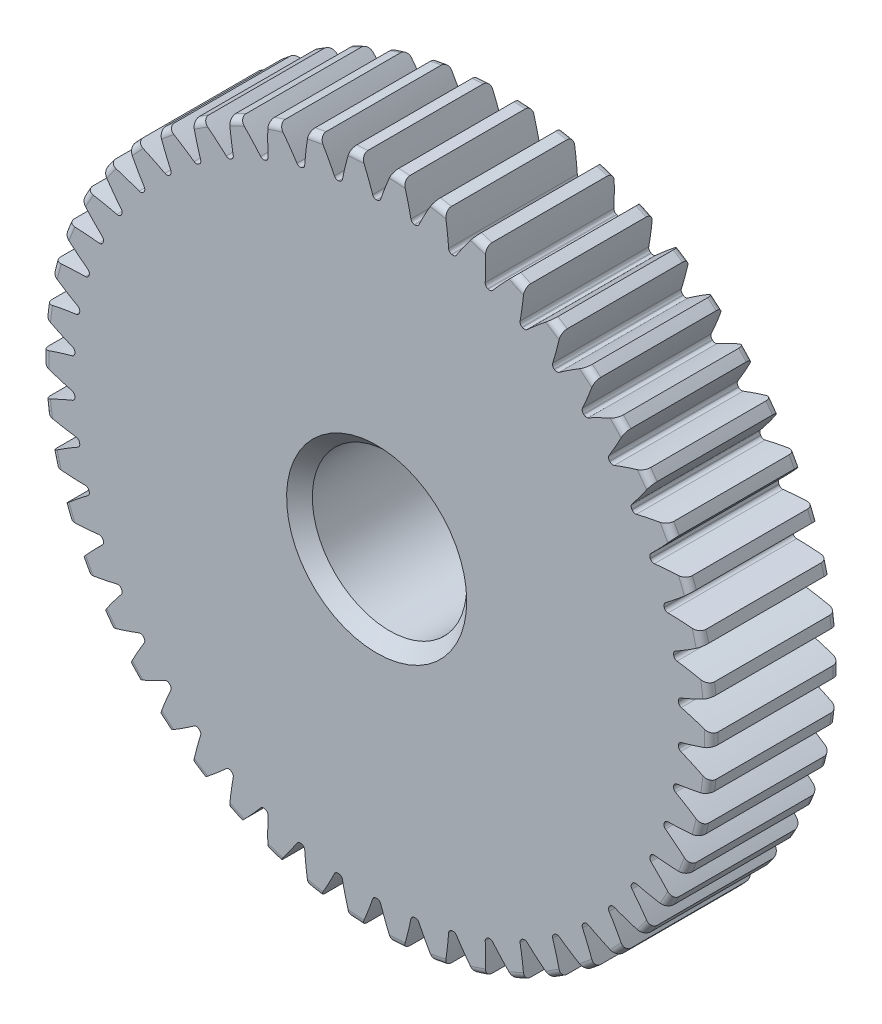
SolidWorks part; units mm, degrees
ref_plane "Front Plane" through (0, 0, 0) normal (0, 0, 1) x (1, 0, 0)
ref_plane "Top Plane" through (0, 0, 0) normal (0, 1, 0) x (1, 0, 0)
ref_plane "Right Plane" through (0, 0, 0) normal (1, 0, 0) x (0, 0, -1)
sketch "Sketch1" plane through (0, 0, 0) normal (0, 0, 1) x (1, 0, 0)
  line L0 (-635, 0) -> (635, 0) construction
  circle A0 centre (0, 0) radius 33.02 construction
  circle A1 centre (0, 0) radius 31.75 construction
  circle A2 centre (0, 0) radius 29.845 construction
  circle A3 centre (0, 0) radius 20.574 construction
  circle A4 centre (0, 0) radius 6.35 construction
  dimension "D2" = 1.27
  dimension "D3" = 3.175
  dimension "D1" = 3.175
sketch "Sketch2" plane through (0, 0, 0) normal (1, 0, 0) x (0, 0, -1)
  line L0 (0, 0) -> (-12.7, 0) construction
  line L1 (-12.7, 0) -> (-25.4, 0) construction
  dimension "Overall Width" = 25.4
  dimension "Face Width" = 12.7
sketch "Sketch4" plane through (0, 0, 0) normal (1, 0, 0) x (0, 0, -1)
  line L0 (-25.4, 6.35) -> (-25.4, 20.574)
  line L1 (-25.4, 20.574) -> (-12.7, 20.574)
  line L2 (-12.7, 20.574) -> (-12.7, 33.02)
  line L3 (-12.7, 33.02) -> (0, 33.02)
  line L4 (0, 33.02) -> (0, 6.35)
  line L5 (-12.7, 20.574) -> (-12.7, 0) construction
  line L6 (0, 33.02) -> (0, -33.02) construction
  line L7 (-12.7, 20.574) -> (0, 20.574) construction
  line L12 (-25.4, 6.35) -> (0, 6.35)
revolve "Revolve1" add sketch "Sketch4" angle 360 about L1
fillet "Fillet2" radius 0.6604 4 edges at (0, 20.574, 25.4) (0, 20.574, 12.7) (0, 33.02, 12.7) (0, 33.02, 0)
sketch "Sketch7" plane through (0, 0, 12.7) normal (0, 0, 1) x (1, 0, 0)
  line L0 (0, 0) -> (0, 33.02) construction
  line L1 (0.9973, 31.7343) -> (1.4979, 32.986) construction
  line L3 (2.0733, 32.9548) -> (1.9936, 31.6873) construction
  line L4 (1.9936, 31.6873) -> (1.874, 29.7861) construction
  line L5 (0, 0) -> (1.874, 29.7861) construction
  line L6 (0.9973, 31.7343) -> (0, 0) construction
  line L7 (0.9973, 31.7343) -> (1.0372, 33.0037) construction
  line L8 (0.9973, 31.7343) -> (0, 0) construction
  circle A0 centre (0, 0) radius 33.02 construction
  arc A1 (-0.035, 29.845) -> (0.035, 29.845) centre (0, 0) cw
  circle A2 centre (0, 0) radius 29.845 construction
  arc A3 (-0.9973, 31.7343) -> (0.9973, 31.7343) centre (0, 0) cw construction
  circle A4 centre (0, 0) radius 31.75 construction
  arc A5 (2.6175, 32.9161) -> (1.5287, 32.9846) centre (0, 0) ccw construction
  arc A6 (0.9973, 31.7343) -> (2.9879, 31.6091) centre (0, 0) cw construction
  arc A7 (-1.5287, 32.9846) -> (1.5287, 32.9846) centre (0, 0) cw
  arc A8 (0.3964, 30.1041) -> (1.5287, 32.9846) centre (30.4767, 19.9434) cw
  arc A9 (-0.3964, 30.1041) -> (-1.5287, 32.9846) centre (-30.4767, 19.9434) ccw
  arc A10 (-0.035, 29.845) -> (-0.3964, 30.1041) centre (-0.0354, 30.226) cw
  arc A11 (0.035, 29.845) -> (0.3964, 30.1041) centre (0.0354, 30.226) ccw
  point P26 (-0.3096, 29.8434)
  point P29 (0.3096, 29.8434)
  dimension "D4" = 0.381
  dimension "D5" = 31.75
  dimension "D3" = 20
  dimension "D1" = 3.9898
  dimension "D2" = 1.9949
extrude "Cut-Extrude2" cut sketch "Sketch7" against normal through all
pattern_circular "CirPattern1" count 50 over 360 about axis through (0, 0, 25.4) along (0, 0, -1) of "Cut-Extrude2"
sketch "Sketch8" plane through (0, 0, 25.4) normal (0, 0, 1) x (1, 0, 0)
  circle A0 centre (0, 0) radius 22.86
  dimension "D1" = 45.72
extrude "Cut-Extrude3" cut sketch "Sketch8" against normal up to surface (12.7 mm away) up to face at (0, 0, 12.7)
sketch "Sketch9" plane through (0, 0, 12.7) normal (0, 0, 1) x (1, 0, 0)
  circle A0 centre (0, 0) radius 7.62
  dimension "D1" = 15.24
extrude "Cut-Extrude4" cut sketch "Sketch9" against normal up to next
chamfer "Chamfer1" distance 1.27 angle 45 1 edges at (7.62, 0, 12.7)
equation "\"D1@Sketch1\"=2.5*(\"Pitch Dia.@Sketch1\"/\"Number of Teeth@Sketch1\")"
equation "\"D1@CirPattern1\"=\"Number of Teeth@Sketch1\""
equation "\"D1@Fillet2\"=\"OD@Sketch1\"*.01"
equation "\"D1@Sketch7\"=3.14159*(\"Pitch Dia.@Sketch1\"/\"Number of Teeth@Sketch1\")"
equation "\"D2@Sketch7\"=\"D1@Sketch7\"/2"
equation "\"D4@Sketch7\"=\"D1@Sketch7\"*.0955"
equation "\"D5@Sketch7\"=\"Pitch Dia.@Sketch1\"/2"
